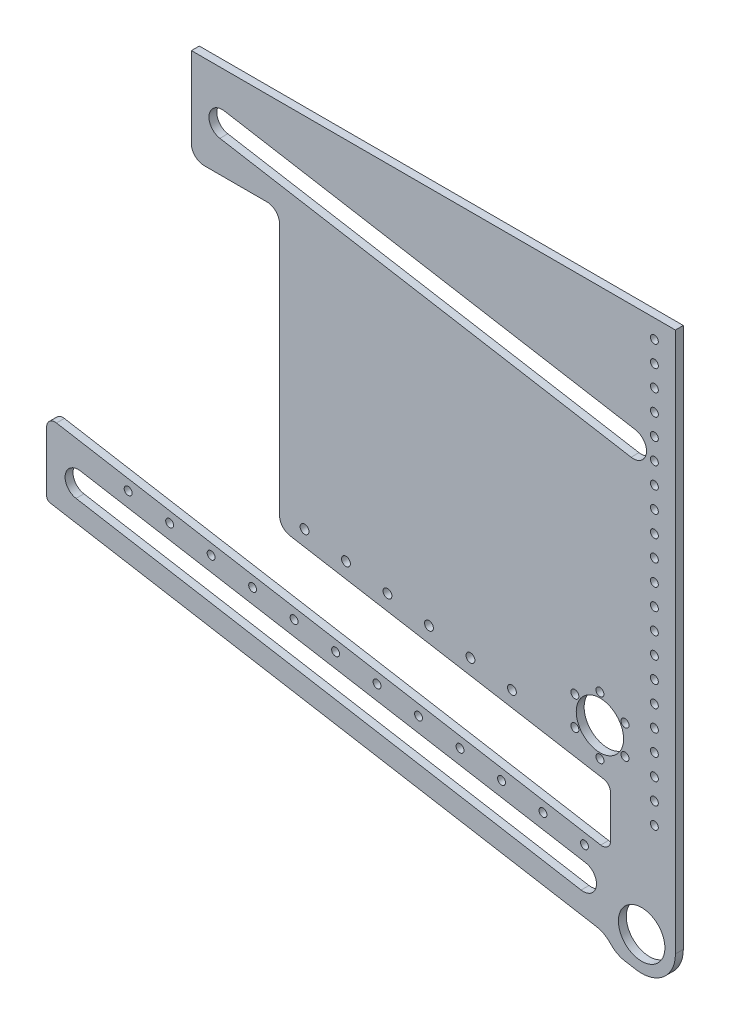
SolidWorks part; units mm, degrees
material "Polypropylene"
ref_plane "Front Plane" through (0, 0, 0) normal (0, 0, 1) x (1, 0, 0)
ref_plane "Top Plane" through (0, 0, 0) normal (0, 1, 0) x (1, 0, 0)
ref_plane "Right Plane" through (0, 0, 0) normal (1, 0, 0) x (0, 0, -1)
sketch "Sketch1" plane through (0, 0, 0) normal (0, 0, 1) x (1, 0, 0)
  line L0 (19.05, 0) -> (19.05, -76.2) construction
  line L1 (0, 19.05) -> (-57.15, 19.05) construction
  line L2 (19.05, -155.575) -> (168.9894, -155.575) construction
  line L3 (0, -95.25) -> (-57.15, -95.25) construction
  line L4 (-57.15, -95.25) -> (-57.15, 19.05) construction
  line L5 (168.9894, 7.239) -> (168.9894, -18.161) construction
  line L6 (168.9894, -18.161) -> (168.9894, -155.575) construction
  line L7 (168.9894, 7.239) -> (143.6189, 6.0141) construction
  line L8 (143.6189, 6.0141) -> (19.05, 0) construction
  line L9 (165.5424, -12.8509) -> (158.8645, -11.7052)
  line L10 (189.3729, 7.239) -> (189.3729, 131.5601)
  line L12 (197.5644, 110.4886) -> (197.5644, -33.1911) construction
  line L16 (-190.0576, 92.9821) -> (-190.0576, 56.7465)
  line L17 (133.7924, 19.9786) -> (-171.0076, 72.2757) construction
  line L18 (132.4501, 12.1554) -> (-172.3499, 64.4526)
  line L19 (135.1346, 27.8017) -> (-169.6654, 80.0989)
  line L20 (-184.1635, 97.9511) -> (139.1268, 42.4814)
  line L23 (-187.9472, 54.2431) -> (141.5847, -2.2975)
  line L24 (176.6729, 131.5601) -> (176.6729, 118.8601) construction
  line L25 (176.6729, 118.8601) -> (189.3729, 118.8601) construction
  line L31 (139.1268, 42.4814) -> (144.2855, 41.5963)
  line L32 (150.2246, 46.6031) -> (150.2246, 72.0031)
  line L38 (146.0036, 77.01) -> (-43.2183, 109.4764)
  line L40 (189.3729, 131.5601) -> (189.3729, 333.3075)
  line L42 (-102.7271, 284.6267) -> (-102.7271, 333.3075)
  line L43 (-102.7271, 333.3075) -> (189.3729, 333.3075)
  line L48 (-49.5497, 116.9867) -> (-49.5497, 269.3867)
  line L49 (-57.1697, 277.0067) -> (-95.1071, 277.0067)
  line L50 (-40.7554, 66.9026) -> (-34.4671, 117.3119) construction
  line L51 (34.3472, 54.0166) -> (40.7189, 104.4154) construction
  line L52 (-34.4671, 117.3119) -> (40.7189, 104.4154) construction
  line L53 (163.9729, 261.2786) -> (-84.1851, 303.8572) construction
  line L54 (162.6306, 253.4554) -> (-85.5274, 296.034)
  line L55 (165.3151, 269.1017) -> (-82.8429, 311.6804)
  arc A0 (19.05, 0) -> (0, 19.05) centre (0, 0) ccw construction
  arc A1 (19.05, -76.2) -> (0, -95.25) centre (0, -76.2) cw construction
  circle A2 centre (168.9894, 7.239) radius 14.0335
  arc A3 (168.9894, -18.161) -> (143.6189, 6.0141) centre (168.9894, 7.239) ccw construction
  arc A4 (165.5424, -12.8509) -> (189.3729, 7.239) centre (168.9894, 7.239) ccw
  arc A5 (132.4501, 12.1554) -> (135.1346, 27.8017) centre (133.7924, 19.9786) ccw
  arc A6 (-169.6654, 80.0989) -> (-172.3499, 64.4526) centre (-171.0076, 72.2757) ccw
  circle A8 centre (176.6729, 118.8601) radius 2.3813
  circle A9 centre (176.6729, 106.1601) radius 2.3813
  circle A10 centre (176.6729, 93.4601) radius 2.3813
  circle A11 centre (176.6729, 80.7601) radius 2.3813
  circle A12 centre (176.6729, 68.0601) radius 2.3813
  circle A15 centre (109.4497, 41.1306) radius 2.3813
  circle A16 centre (84.4155, 45.4259) radius 2.3812
  circle A17 centre (59.3813, 49.7212) radius 2.3813
  circle A18 centre (34.3472, 54.0166) radius 2.3813
  circle A19 centre (9.313, 58.3119) radius 2.3813
  circle A20 centre (-15.7212, 62.6072) radius 2.3812
  circle A21 centre (-40.7554, 66.9026) radius 2.3813
  circle A22 centre (-65.7896, 71.1979) radius 2.3813
  circle A23 centre (-90.8237, 75.4932) radius 2.3812
  circle A24 centre (-115.8579, 79.7886) radius 2.3813
  circle A25 centre (-140.8921, 84.0839) radius 2.3812
  circle A28 centre (134.4839, 36.8353) radius 2.3813
  arc A31 (-187.9472, 54.2431) -> (-190.0576, 56.7465) centre (-187.5176, 56.7465) cw
  arc A34 (158.8645, -11.7052) -> (150.2246, -7.0013) centre (161.4417, 3.3154) cw
  circle A39 centre (143.8098, 103.921) radius 21.9964 construction
  circle A40 centre (143.8098, 103.921) radius 14.2875
  circle A41 centre (143.8098, 103.921) radius 17.4625 construction
  circle A42 centre (143.8098, 121.3835) radius 2.413
  circle A43 centre (158.9328, 112.6523) radius 2.413
  circle A44 centre (158.9328, 95.1898) radius 2.413
  circle A45 centre (143.8098, 86.4585) radius 2.413
  circle A46 centre (128.6869, 95.1898) radius 2.413
  circle A47 centre (128.6869, 112.6523) radius 2.413
  arc A48 (141.5847, -2.2975) -> (150.2246, -7.0013) centre (139.0075, -17.318) cw
  arc A49 (144.2855, 41.5963) -> (150.2246, 46.6031) centre (145.1446, 46.6031) ccw
  arc A53 (-190.0576, 92.9821) -> (-184.1635, 97.9511) centre (-185.016, 92.9821) cw
  arc A55 (150.2246, 72.0031) -> (146.0036, 77.01) centre (145.1446, 72.0031) ccw
  circle A57 centre (176.6729, 131.5601) radius 2.3813
  circle A58 centre (176.6729, 144.2601) radius 2.3813
  circle A59 centre (176.6729, 156.9601) radius 2.3813
  circle A60 centre (176.6729, 169.6601) radius 2.3813
  circle A61 centre (176.6729, 182.3601) radius 2.3813
  circle A62 centre (176.6729, 195.0601) radius 2.3813
  circle A63 centre (176.6729, 207.7601) radius 2.3813
  circle A64 centre (176.6729, 220.4601) radius 2.3813
  circle A65 centre (176.6729, 233.1601) radius 2.3813
  circle A66 centre (176.6729, 245.8601) radius 2.3813
  circle A67 centre (176.6729, 258.5601) radius 2.3813
  circle A68 centre (176.6729, 271.2601) radius 2.3813
  circle A69 centre (176.6729, 283.9601) radius 2.3813
  circle A70 centre (176.6729, 296.6601) radius 2.3813
  circle A71 centre (176.6729, 309.3601) radius 2.3813
  circle A72 centre (176.6729, 322.0601) radius 2.3813
  arc A79 (-43.2183, 109.4764) -> (-49.5497, 116.9867) centre (-41.9297, 116.9867) cw
  arc A80 (-102.7271, 284.6267) -> (-95.1071, 277.0067) centre (-95.1071, 284.6267) ccw
  arc A81 (-49.5497, 269.3867) -> (-57.1697, 277.0067) centre (-57.1697, 269.3867) ccw
  circle A84 centre (-9.4327, 113.0178) radius 2.667
  circle A86 centre (15.6017, 108.7237) radius 2.667
  circle A88 centre (40.636, 104.4296) radius 2.667
  circle A90 centre (65.6704, 100.1355) radius 2.667
  circle A92 centre (90.7048, 95.8414) radius 2.667
  circle A94 centre (-34.4671, 117.3119) radius 2.667
  arc A95 (162.6306, 253.4554) -> (165.3151, 269.1017) centre (163.9729, 261.2786) ccw
  arc A96 (-82.8429, 311.6804) -> (-85.5274, 296.034) centre (-84.1851, 303.8572) ccw
  point P24 (-18.6076, 46.1272)
  point P51 (-190.0576, 48.1625)
  point P92 (143.8191, 3.8303)
  point P95 (150.6057, -10.2881)
  point P107 (-190.0576, 98.9625)
  point P118 (143.8098, 103.921)
  point P159 (-202.7576, 77.01)
  point P162 (39.8939, 282.5679)
  dimension "D1" = 19.05
  dimension "D4" = 19.05
  dimension "D6" = 28.067
  dimension "D7" = 50.8
  dimension "D15" = 7.9375
  dimension "D24" = 4.7625
  dimension "D26" = 2.54
  dimension "D27" = 15.24
  dimension "D31" = 43.9928
  dimension "D32" = 34.925
  dimension "D34" = 4.826
  dimension "D19" = 28.575
  dimension "D25" = 5.08
  dimension "D30" = 5.08
  dimension "D21" = 7.62
  dimension "D2" = 155.575
  dimension "D3" = 76.2
  dimension "D5" = 114.3
  dimension "D8" = 137.414
  dimension "D9" = 124.714
  dimension "D10" = 6.35
  dimension "D11" = 12.5
  dimension "D12" = 355.6
  dimension "D14" = 50.8
  dimension "D13" = 28.575
  dimension "D16" = 19.05
  dimension "D18" = 304.8
  dimension "D22" = 12.7
  dimension "D28" = 12.7
  dimension "D37" = 292.1
  dimension "D33" = 50.8
  dimension "D38" = 25.4
  dimension "D39" = 12.7
  dimension "D17" = 55.5805
  dimension "D29" = 12.7
  dimension "D40" = 17.2798
  dimension "D41" = 9.4076
  dimension "D42" = 39.1483
  dimension "D43" = 152.4
  dimension "D44" = 241.3
  dimension "D45" = 248.158
  dimension "D46" = 25.4
  dimension "D23" = 5
  dimension "D20" = 2
  dimension "D36" = 17
  dimension "D35" = 6
extrude "Boss-Extrude1" add sketch "Sketch1" along normal blind 4.7625
sketch "Sketch2" plane through (0, 0, 4.7625) normal (0, 0, 1) x (1, 0, 0)
  line L0 (-188.8187, 48.0143) -> (-189.0355, 50.6158)
  line L1 (-189.2877, 50.8909) -> (-190.3122, 51.0667)
  line L2 (-190.6416, 50.8914) -> (-191.7133, 48.5109)
  line L3 (-191.7725, 48.4567) -> (-191.7682, 48.4817) construction
  line L4 (-189.7999, 50.9788) -> (-190.2767, 48.2) construction
  line L5 (-188.7766, 49.257) -> (-191.3387, 49.6966) construction
  line L6 (158.8645, -11.7052) -> (165.5424, -12.8509) construction
  line L7 (-191.1909, 49.6712) -> (-191.4434, 48.2) construction
  line L8 (-188.9244, 49.2823) -> (-189.1101, 48.2) construction
  line L11 (-188.7809, 47.9434) -> (-191.7725, 48.4567)
  line L13 (-188.7766, 47.9684) -> (-188.306, 47.8877)
  line L14 (-188.306, 47.8877) -> (-188.3103, 47.8626)
  line L15 (-188.3103, 47.8626) -> (-188.7809, 47.9434)
  line L16 (-188.7809, 47.9434) -> (-188.7766, 47.9684) construction
  line L17 (-192.2389, 48.5625) -> (-192.2431, 48.5374)
  line L18 (-192.2431, 48.5374) -> (-191.7725, 48.4567)
  line L19 (-191.7682, 48.4817) -> (-192.2389, 48.5625)
  line L21 (-190.0576, 92.9821) -> (-190.0576, 56.7465) construction
  arc A0 (-190.3122, 51.0667) -> (-190.6416, 50.8914) centre (-190.3637, 50.7663) ccw
  arc A1 (-189.0355, 50.6158) -> (-189.2877, 50.8909) centre (-189.3392, 50.5905) ccw
  arc A2 (-191.7682, 48.4817) -> (-191.7133, 48.5109) centre (-191.7596, 48.5318) ccw
  arc A3 (-188.8187, 48.0143) -> (-188.7766, 47.9684) centre (-188.768, 48.0185) ccw
  point P6 (-190.0576, 49.4768)
  dimension "D1" = 0.0254
  dimension "Root_fillet" = 0.3048
  dimension "Break_rad" = 0.0508
  dimension "Gap_width" = 2.2997
  dimension "Dedendum" = 1.524
  dimension "Addendum_plus" = 1.2954
  dimension "Pressure_angle" = 14.5
  dimension "D2" = 0.4775
equation "\"D18@Sketch1\"=13.25-1.25"
equation "\"D12@Sketch1\"=15.25-1.25"
equation "\"D45@Sketch1\"=12.00-1.48-0.75"
